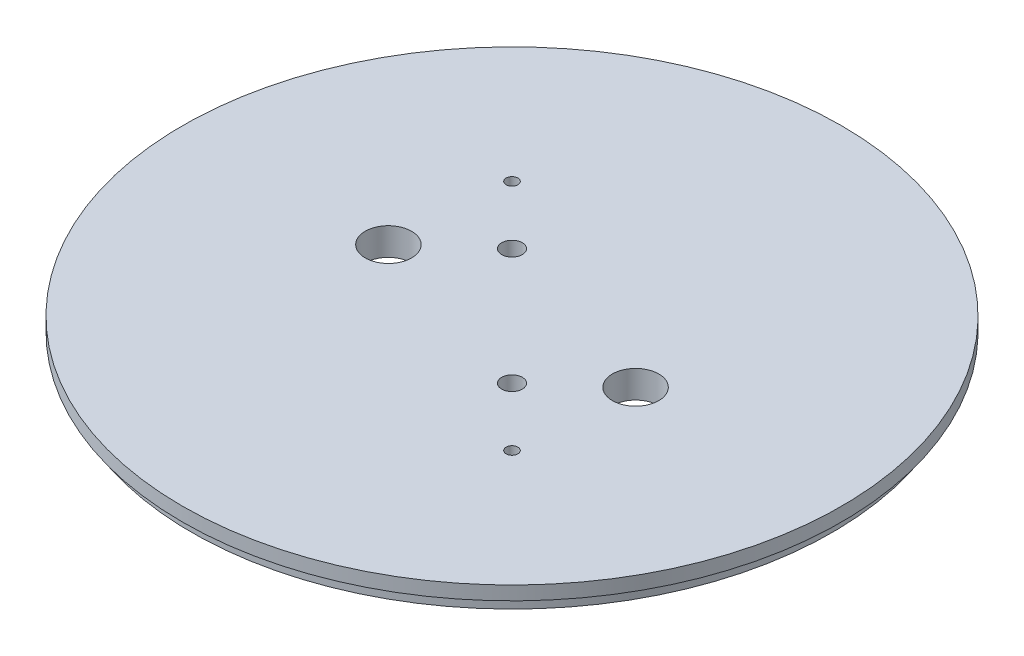
SolidWorks part; units mm, degrees
material "6061-T6 (SS)"
ref_plane "Front Plane" through (0, 0, 0) normal (0, 0, 1) x (1, 0, 0)
ref_plane "Top Plane" through (0, 0, 0) normal (0, 1, 0) x (1, 0, 0)
ref_plane "Right Plane" through (0, 0, 0) normal (1, 0, 0) x (0, 0, -1)
sketch "Sketch1" plane through (0, 0, 0) normal (0, 1, 0) x (1, 0, 0)
  line L0 (0, -76.2) -> (0, 76.2) construction
  line L1 (-76.2, 0) -> (76.2, 0) construction
  line L2 (-26.9408, 26.9408) -> (0, 0) construction
  line L3 (0, 56.7387) -> (0, 29.6936) construction
  line L4 (3.6407, 56.7387) -> (3.6407, 29.6936) construction
  line L5 (-3.6407, 56.7387) -> (-3.6407, 29.6936) construction
  line L6 (0, -56.7387) -> (0, -29.6936) construction
  line L7 (3.6407, -56.7387) -> (3.6407, -29.6936) construction
  line L8 (-3.6407, -56.7387) -> (-3.6407, -29.6936) construction
  line L9 (-53.8815, -53.8815) -> (54.3236, 54.3236) construction
  circle A0 centre (0, 0) radius 76.2
  circle A1 centre (0, 0) radius 3.175 construction
  circle A2 centre (28.575, 0) radius 5.3578
  circle A3 centre (-28.575, 0) radius 5.3578
  circle A4 centre (-26.9408, 26.9408) radius 1.3589
  arc A6 (3.6407, 56.7387) -> (-3.6407, 56.7387) centre (0, 56.7387) ccw construction
  arc A7 (-3.6407, 29.6936) -> (3.6407, 29.6936) centre (0, 29.6936) ccw construction
  arc A8 (3.6407, -56.7387) -> (-3.6407, -56.7387) centre (0, -56.7387) cw construction
  arc A9 (-3.6407, -29.6936) -> (3.6407, -29.6936) centre (0, -29.6936) cw construction
  circle A10 centre (26.9408, -26.9408) radius 1.3589
  circle A11 centre (-13.4704, 13.4704) radius 2.3813
  circle A12 centre (13.4704, -13.4704) radius 2.3813
  point P16 (0, 43.2162)
  point P19 (0, 0)
  point P26 (0, -43.2162)
  dimension "D1" = 152.4
  dimension "D2" = 6.35
  dimension "D3" = 10.7156
  dimension "D5" = 2.7178
  dimension "D8" = 4.7625
  dimension "D6" = 38.1
  dimension "D7" = 45
  dimension "D4" = 45
  dimension "D9" = 28.575
extrude "Boss-Extrude1" add sketch "Sketch1" along normal blind 6.35
sketch "Sketch2" plane through (0, 0, 0) normal (0, -1, 0) x (1, 0, 0)
  circle A0 centre (0, 0) radius 76.2
  circle A1 centre (0, 0) radius 74.041
  dimension "D1" = 152.4
  dimension "D2" = 148.082
extrude "Cut-Extrude1" cut sketch "Sketch2" against normal blind 3.175
sketch "Sketch3" plane through (0, 6.35, 0) normal (0, 1, 0) x (1, 0, 0)
  line L0 (0, 76.2) -> (0, -76.2) construction
  line L1 (-76.2, 0) -> (76.2, 0) construction
  line L2 (0, 34.798) -> (0, 13.97) construction
  line L3 (3.2385, 34.798) -> (3.2385, 13.97)
  line L4 (-3.2385, 34.798) -> (-3.2385, 13.97)
  line L5 (0, -34.798) -> (0, -13.97) construction
  line L6 (3.2385, -34.798) -> (3.2385, -13.97)
  line L7 (-3.2385, -34.798) -> (-3.2385, -13.97)
  circle A0 centre (0, 0) radius 76.2 construction
  arc A1 (3.2385, 34.798) -> (-3.2385, 34.798) centre (0, 34.798) ccw
  arc A2 (-3.2385, 13.97) -> (3.2385, 13.97) centre (0, 13.97) ccw
  arc A3 (3.2385, -34.798) -> (-3.2385, -34.798) centre (0, -34.798) cw
  arc A4 (-3.2385, -13.97) -> (3.2385, -13.97) centre (0, -13.97) cw
  point P7 (0, 13.97)
  point P8 (0, 34.798)
  point P12 (0, 24.384)
  point P20 (0, -24.384)
  point P25 (0, -34.798)
  point P26 (0, -13.97)
  dimension "D1" = 13.97
  dimension "D2" = 20.828
  dimension "D3" = 6.477
extrude "Cut-Extrude2" cut sketch "Sketch3" against normal blind 3.556 from offset 5.969 offset against normal yes
equation "\"leadDist\"=1.5"
equation "\"Lead_Screw_Dist\" = 2.25in"
equation "\"D9@Sketch1\"=\"Lead_Screw_Dist\"/2"
equation "\"Lead_Screw_Diam\" = (27/64)*1in"
equation "\"D3@Sketch1\"=\"Lead_Screw_Diam\""
